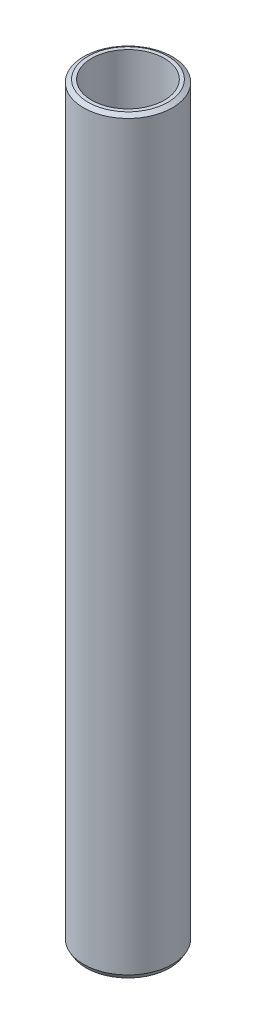
SolidWorks part; units mm, degrees
ref_plane "Front Plane" through (0, 0, 0) normal (0, 0, 1) x (1, 0, 0)
ref_plane "Top Plane" through (0, 0, 0) normal (0, 1, 0) x (1, 0, 0)
ref_plane "Right Plane" through (0, 0, 0) normal (1, 0, 0) x (0, 0, -1)
sketch "Sketch1" plane through (0, 0, 0) normal (0, 1, 0) x (1, 0, 0)
  circle A0 centre (0, 0) radius 32.5
  dimension "SHAFT_OD" = 65
extrude "Boss-Extrude1" add sketch "Sketch1" along normal blind 548.4002
sketch "Sketch2" plane through (0, 0, 0) normal (0, 1, 0) x (1, 0, 0)
  circle A0 centre (0, 0) radius 26.6193
  dimension "BORE_D" = 53.2387
extrude "Cut-Extrude1" cut sketch "Sketch2" along normal through all
chamfer "Chamfer1" distance 1.8846 angle 60 2 edges at (0, 548.4002, 32.5) (0, 0, 32.5) first distance on face at (0, 548.4002, 32.5) first distance on face at (0, 0, 26.6193)
